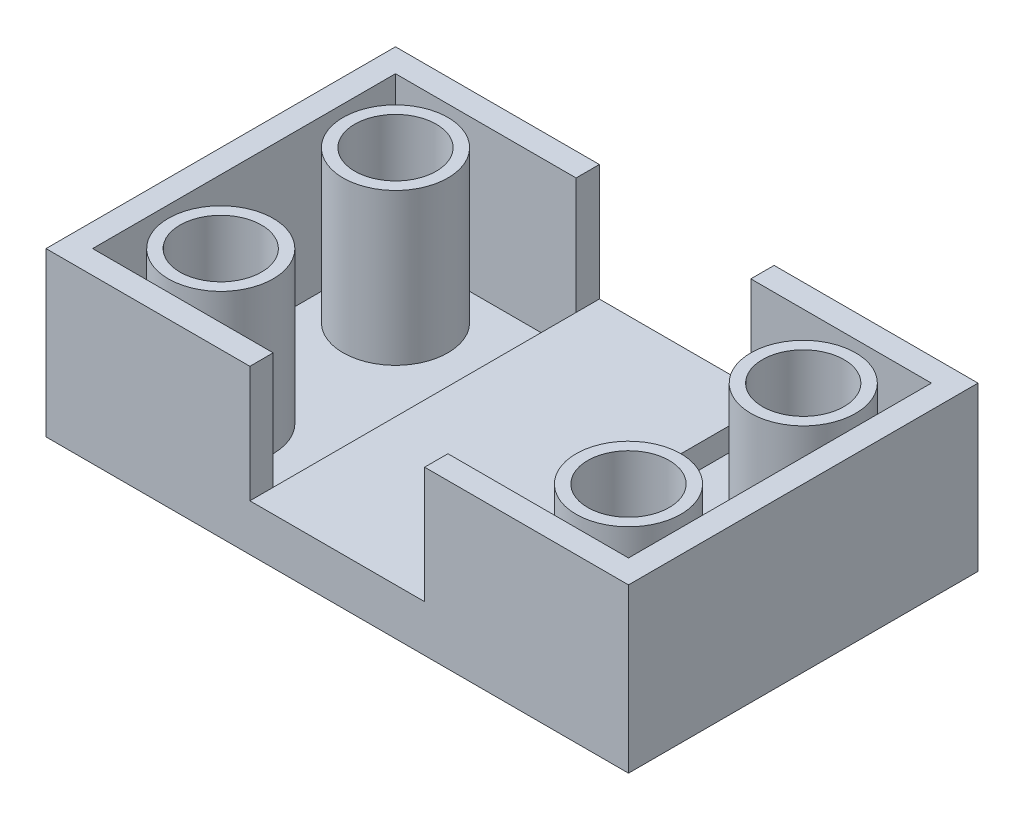
SolidWorks part; units mm, degrees
ref_plane "Front Plane" through (0, 0, 0) normal (0, 0, 1) x (1, 0, 0)
ref_plane "Top Plane" through (0, 0, 0) normal (0, 1, 0) x (1, 0, 0)
ref_plane "Right Plane" through (0, 0, 0) normal (1, 0, 0) x (0, 0, -1)
sketch "Sketch1" plane through (0, 0, 0) normal (0, 1, 0) x (1, 0, 0)
  line L0 (0, 25.3195) -> (0, 0) construction
  line L1 (25, -15) -> (-25, -15)
  line L2 (25, -15) -> (25, 15)
  line L3 (25, 15) -> (-25, 15)
  line L4 (-25, -15) -> (-25, 15)
  line L5 (25, -15) -> (-25, 15) construction
  line L6 (25, 15) -> (-25, -15) construction
  line L7 (0, 0) -> (-45.4624, 0) construction
  circle A0 centre (-17.5, 7.5) radius 2.5
  circle A1 centre (17.5, 7.5) radius 2.5
  circle A2 centre (17.5, -7.5) radius 2.5
  circle A3 centre (-17.5, -7.5) radius 2.5
  point P0 (0, 0)
  dimension "D3" = 5
  dimension "D1" = 30
  dimension "D2" = 50
  dimension "D4" = 7.5
  dimension "D5" = 7.5
extrude "Boss-Extrude1" add sketch "Sketch1" along normal blind 15
sketch "Sketch2" plane through (0, 15, 0) normal (0, 1, 0) x (1, 0, 0)
  line L0 (25, 15) -> (-25, 15) construction
  line L1 (7.5, -15) -> (-7.5, -15)
  line L2 (7.5, -15) -> (7.5, 15)
  line L3 (7.5, 15) -> (-7.5, 15)
  line L4 (-7.5, -15) -> (-7.5, 15)
  line L5 (7.5, -15) -> (-7.5, 15) construction
  line L6 (7.5, 15) -> (-7.5, -15) construction
  point P0 (0, 0)
  dimension "D1" = 15
extrude "Cut-Extrude1" cut sketch "Sketch2" against normal blind 10
chamfer "Chamfer1" distance 0.75 angle 60 4 edges at (17.5, 0, 10) (17.5, 0, -10) (-17.5, 0, 5) (-17.5, 0, -5) first distance on face at (17.5, 15, 10) first distance on face at (17.5, 15, -10) first distance on face at (-17.5, 15, 5) first distance on face at (-17.5, 15, -5)
shell "Shell1" thickness 2 removed face at (7.5, 10, 0) removed face at (-7.5, 10, 0) removed face at (16.25, 15, 0) removed face at (-16.25, 15, 0)
sketch "Sketch3" plane through (0, 15, 0) normal (0, 1, 0) x (1, 0, 0)
  circle A0 centre (-17.5, -7.5) radius 3.5
  dimension "D1" = 7
extrude "Cut-Extrude2" cut sketch "Sketch3" against normal blind 5
sketch "Sketch4" plane through (0, 15, 0) normal (0, 1, 0) x (1, 0, 0)
  circle A0 centre (-17.5, 7.5) radius 3.5
  dimension "D1" = 7
extrude "Cut-Extrude3" cut sketch "Sketch4" against normal blind 5
sketch "Sketch5" plane through (0, 15, 0) normal (0, 1, 0) x (1, 0, 0)
  circle A0 centre (17.5, 7.5) radius 3.5
  dimension "D1" = 7
extrude "Cut-Extrude4" cut sketch "Sketch5" against normal blind 5
sketch "Sketch6" plane through (0, 15, 0) normal (0, 1, 0) x (1, 0, 0)
  circle A0 centre (17.5, -7.5) radius 3.5
  dimension "D1" = 7
extrude "Cut-Extrude5" cut sketch "Sketch6" against normal blind 5
chamfer "Chamfer2" distance 1 angle 45 4 edges at (25, 0, 0) (0, 0, -15) (-25, 0, 0) (0, 0, 15)
